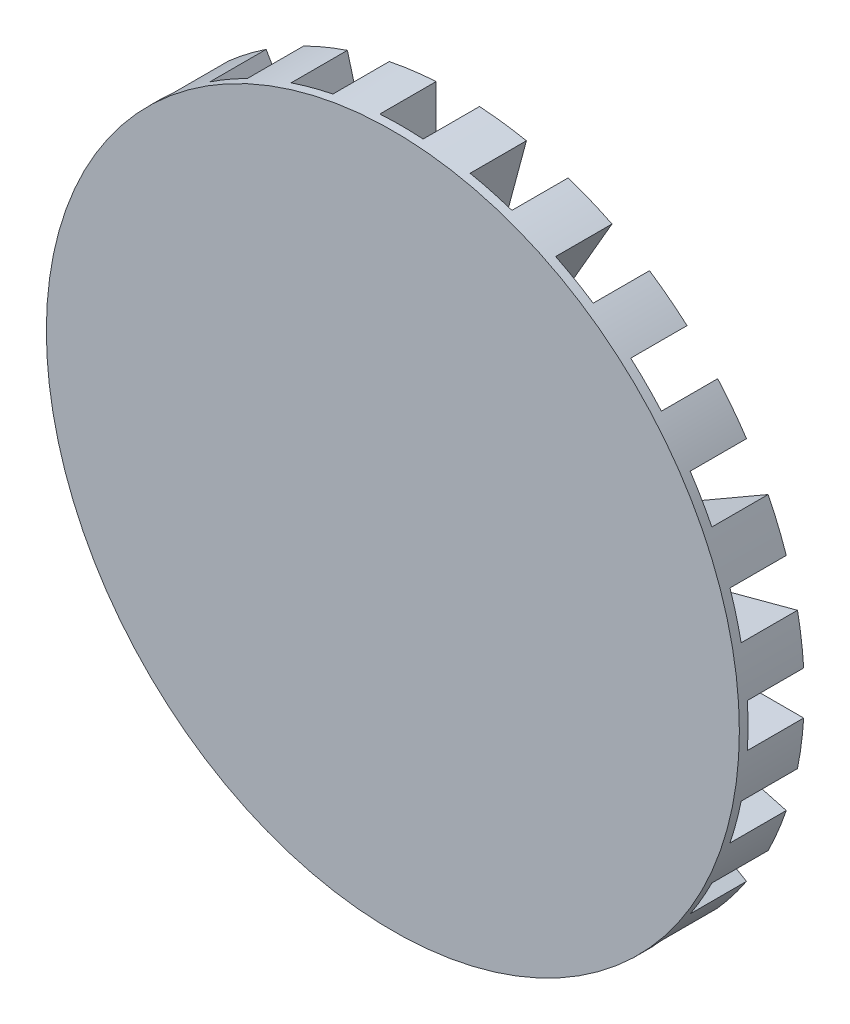
SolidWorks part; units mm, degrees
material "PUR"
ref_plane "Front Plane" through (0, 0, 0) normal (0, 0, 1) x (1, 0, 0)
ref_plane "Top Plane" through (0, 0, 0) normal (0, 1, 0) x (1, 0, 0)
ref_plane "Right Plane" through (0, 0, 0) normal (1, 0, 0) x (0, 0, -1)
sketch "Sketch1" plane through (0, 0, 0) normal (0, 0, 1) x (1, 0, 0)
  circle A0 centre (0, 0) radius 80
  circle A1 centre (0, 0) radius 100 construction
  circle A4 centre (0, 0) radius 100 construction
  dimension "D1" = 20
extrude "Boss-Extrude1" add sketch "Sketch1" along normal blind 2 from offset 13
sketch "Sketch3" plane through (0, 0, 15) normal (0, 0, 1) x (1, 0, 0)
  line L0 (0, 0) -> (0, -80) construction
  line L1 (0, 0) -> (-20.7055, -77.2741) construction
  line L2 (-5, -79.8436) -> (-5, -37.9788)
  line L3 (-5, -37.9788) -> (-15.8354, -78.4171)
  line L4 (-5, -58.9112) -> (0, -58.9112) construction
  line L5 (-10.4177, -58.1979) -> (-15.2473, -56.9038) construction
  circle A0 centre (0, 0) radius 80 construction
  arc A1 (-5, -79.8436) -> (-15.8354, -78.4171) centre (0, 0) cw
  dimension "D1" = 10
  dimension "D2" = 15
extrude "Boss-Extrude2" add sketch "Sketch3" against normal up to surface (15 mm away)
pattern_circular "CirPattern1" count 24 over 360 about axis through (0, 0, 15) along (0, 0, -1) of "Boss-Extrude2"
